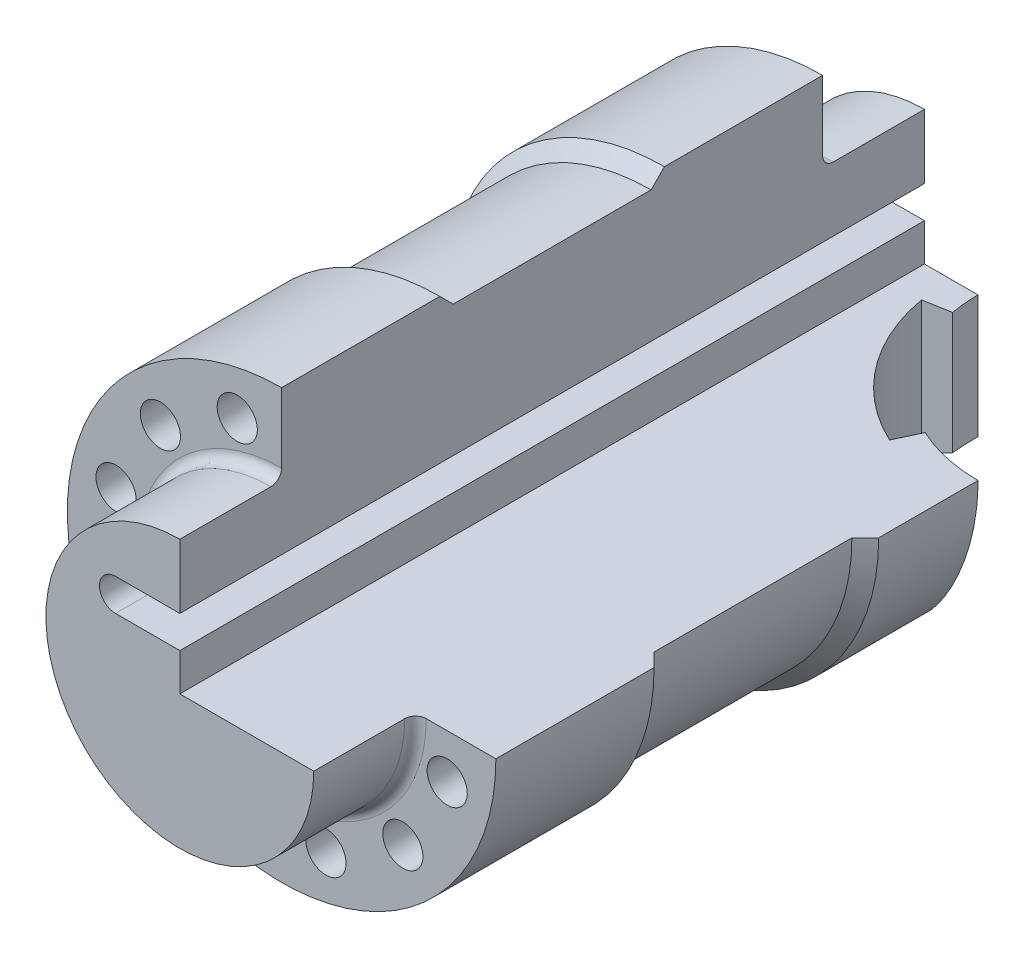
SolidWorks part; units mm, degrees
material "AISI 1020 Steel, Cold Rolled"
ref_plane "Front Plane" through (0, 0, 0) normal (0, 0, 1) x (1, 0, 0)
ref_plane "Top Plane" through (0, 0, 0) normal (0, 1, 0) x (1, 0, 0)
ref_plane "Right Plane" through (0, 0, 0) normal (1, 0, 0) x (0, 0, -1)
sketch "Sketch1" plane through (0, 0, 0) normal (0, 0, 1) x (1, 0, 0)
  circle A0 centre (0, 0) radius 37.5
  dimension "D1" = 75
extrude "Boss-Extrude1" add sketch "Sketch1" along normal blind 50.5 and the other way blind 50.5
sketch "Sketch2" plane through (0, 0, 50.5) normal (0, 0, 1) x (1, 0, 0)
  circle A0 centre (0, 0) radius 40
  dimension "D1" = 80
extrude "Boss-Extrude2" add sketch "Sketch2" against normal blind 28.5
chamfer "Chamfer1" distance 3.535 angle 45 1 edges at (37.5, 0, 22)
mirror "Mirror1" about plane through (0, 0, 0) normal (0, 0, 1) of "Chamfer1", "Boss-Extrude2"
sketch "Sketch3" plane through (0, 0, -50.5) normal (0, 0, -1) x (-1, 0, 0)
  circle A0 centre (0, 0) radius 25
  dimension "D1" = 50
extrude "Boss-Extrude3" add sketch "Sketch3" along normal blind 19
fillet "Fillet1" radius 2 1 edges at (-25, 0, -50.5)
sketch "Sketch4" plane through (0, 0, 50.5) normal (0, 0, 1) x (1, 0, 0)
  circle A0 centre (0, 0) radius 25
  dimension "D1" = 50
extrude "Boss-Extrude4" add sketch "Sketch4" along normal blind 19
fillet "Fillet2" radius 2 1 edges at (25, 0, 50.5)
ref_plane "Plane1" through (0, 0, 69.5) normal (0, 0, 1) x (1, 0, 0)
sketch "Sketch5" plane through (0, 0, 69.5) normal (0, 0, 1) x (1, 0, 0)
  line L0 (0, 0) -> (0, 7)
  line L1 (0, 0) -> (40, 0)
  line L2 (0, 10) -> (-12, 10) construction
  line L3 (0, 7) -> (-12, 7)
  line L4 (0, 13) -> (-12, 13)
  line L5 (0, 13) -> (0, 40)
  circle A0 centre (0, 0) radius 40 construction
  arc A2 (-12, 13) -> (-12, 7) centre (-12, 10) ccw
  arc A3 (0, 40) -> (40, 0) centre (0, 0) cw
  point P9 (-6, 10)
  dimension "D2" = 3
  dimension "D1" = 12
  dimension "D3" = 7
extrude "Cut-Extrude1" cut sketch "Sketch5" against normal through all
sketch "Sketch6" plane through (0, 0, 0) normal (0, 1, 0) x (1, 0, 0)
  line L0 (25, 69.5) -> (40, 69.5) construction
  line L1 (40, 69.5) -> (40, 50.5) construction
  circle A0 centre (40, 69.5) radius 30
  dimension "D2" = 60
  dimension "D1" = 90
extrude "Cut-Extrude2" cut sketch "Sketch6" against normal through all
sketch "Sketch7" plane through (0, 0, 0) normal (0, 1, 0) x (1, 0, 0)
  line L0 (5.5317, 63.4223) -> (10.4558, 64.2906)
  line L1 (25.2084, 37.7792) -> (27.3215, 42.3108)
  line L2 (0, 69.5) -> (10, 69.5) construction
  line L3 (40, 39.5) -> (40, 20.965) construction
  arc A0 (5.5317, 63.4223) -> (25.2084, 37.7792) centre (40, 69.5) ccw
  arc A1 (10, 69.5) -> (40, 39.5) centre (40, 69.5) ccw construction
  arc A2 (10.4558, 64.2906) -> (27.3215, 42.3108) centre (40, 69.5) ccw
  dimension "D3" = 70
  dimension "D1" = 10
  dimension "D2" = 25
extrude "Cut-Extrude3" cut sketch "Sketch7" against normal through all
sketch "Sketch8" plane through (0, 0, 50.5) normal (0, 0, 1) x (1, 0, 0)
  line L0 (0, 0) -> (-11.7269, 43.7654) construction
  line L1 (0, 40) -> (0, 27) construction
  circle A0 centre (-8.2822, 30.9096) radius 3.75
  circle A1 centre (-22.6274, 22.6274) radius 3.75
  circle A2 centre (-30.9096, 8.2822) radius 3.75
  circle A3 centre (-30.9096, -8.2822) radius 3.75
  circle A4 centre (-22.6274, -22.6274) radius 3.75
  circle A5 centre (-8.2822, -30.9096) radius 3.75
  circle A6 centre (8.2822, -30.9096) radius 3.75
  circle A7 centre (22.6274, -22.6274) radius 3.75
  circle A8 centre (30.9096, -8.2822) radius 3.75
  point P26 (0, 0)
  dimension "D1" = 7.5
  dimension "D4" = 9
  dimension "D2" = 15
  dimension "D3" = 32
extrude "Cut-Extrude4" cut sketch "Sketch8" against normal through all
equation "\"A\"= 139"
equation "\"B\"= 19"
equation "\"C\"= 28.5"
